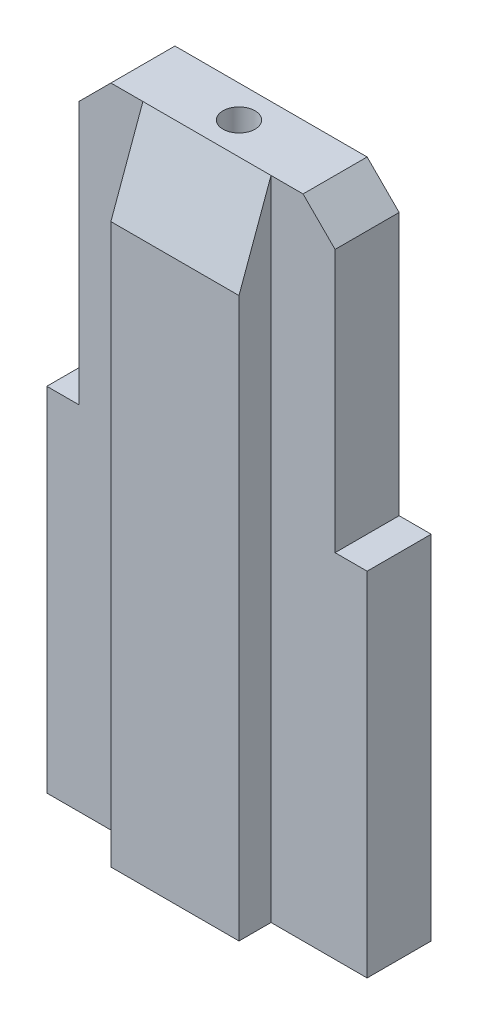
SolidWorks part; units mm, degrees
material "Perspex (TM) GS Acrylic Cast Sheet"
ref_plane "Ebene vorne" through (0, 0, 0) normal (0, 0, 1) x (1, 0, 0)
ref_plane "Ebene oben" through (0, 0, 0) normal (0, 1, 0) x (1, 0, 0)
ref_plane "Ebene rechts" through (0, 0, 0) normal (1, 0, 0) x (0, 0, -1)
sketch "Skizze1" plane through (0, 0, 0) normal (0, 0, 1) x (1, 0, 0)
  line L0 (0, 13.4182) -> (0, -13.9929) construction
  line L1 (-2, 2.75) -> (-2, 7.35)
  line L2 (-2.5, 2.75) -> (-2, 2.75)
  line L3 (-2.5, 2.75) -> (-2.5, -2.75)
  line L4 (-2.5, -2.75) -> (2.5, -2.75)
  line L5 (2.5, 2.75) -> (2.5, -2.75)
  line L6 (-2.5, 2.75) -> (2.5, -2.75) construction
  line L7 (-2.5, -2.75) -> (2.5, 2.75) construction
  line L8 (-2, 7.35) -> (2, 7.35)
  line L9 (2, 7.35) -> (2, 2.75)
  line L10 (2, 2.75) -> (2.5, 2.75)
  point P3 (0, 0)
  dimension "D1" = 5.5
  dimension "D2" = 5
  dimension "D3" = 4
  dimension "D4" = 2
  dimension "D5" = 4.6
extrude "Aufsatz-Linear austragen1" add sketch "Skizze1" along normal mid plane 1
sketch "Skizze2" plane through (0, 0, 0.5) normal (0, 0, 1) x (1, 0, 0)
  line L0 (-2.5, -2.75) -> (2.5, -2.75) construction
  line L1 (-1, 7.35) -> (1, 7.35)
  line L2 (-1, 7.35) -> (-1, -2.75)
  line L3 (-1, -2.75) -> (1, -2.75)
  line L4 (1, 7.35) -> (1, -2.75)
  line L5 (-1, 7.35) -> (1, -2.75) construction
  line L6 (-1, -2.75) -> (1, 7.35) construction
  line L7 (-2, 7.35) -> (-2, 2.75) construction
  point P0 (0, 2.3)
  dimension "D1" = 2
  dimension "D2" = 10.1
  dimension "D3" = 2
extrude "Aufsatz-Linear austragen2" add sketch "Skizze2" along normal blind 0.5
chamfer "Fase1" distance 0.5 angle 70 1 edges at (0, 7.35, 1) first distance on face at (0.125, 7.35, 0.4375)
sketch "Skizze3" plane through (0, 0, -0.5) normal (0, 0, -1) x (-1, 0, 0)
  line L0 (2.5, -2.75) -> (-2.5, -2.75) construction
  line L1 (-1, 7.35) -> (1, 7.35)
  line L2 (-1, 7.35) -> (-1, -2.75)
  line L3 (-1, -2.75) -> (1, -2.75)
  line L4 (1, 7.35) -> (1, -2.75)
  line L5 (-1, 7.35) -> (1, -2.75) construction
  line L6 (-1, -2.75) -> (1, 7.35) construction
  line L7 (2.5, 2.75) -> (2.5, -2.75) construction
  point P0 (0, 2.3)
  dimension "D1" = 10.1
  dimension "D2" = 2
  dimension "D3" = 2.5
extrude "Aufsatz-Linear austragen3" add sketch "Skizze3" along normal blind 0.5
chamfer "Fase3" distance 0.5 angle 70 1 edges at (0, 7.35, -1) first distance on face at (0.1, 7.35, -0.25)
chamfer "Fase4" distance 0.5 angle 45 1 edges at (-2, 7.35, 0)
chamfer "Fase5" distance 0.5 angle 45 1 edges at (2, 7.35, 0)
sketch "Skizze4" plane through (0, 7.35, 0) normal (0, 1, 0) x (1, 0, 0)
  circle A0 centre (0, 0) radius 0.25
  dimension "D1" = 0.5
extrude "Schnitt-Linear austragen1" cut sketch "Skizze4" against normal through all
ref_axis "Achse1" through (0, -2.75, 0) along (0, 1, 0)
